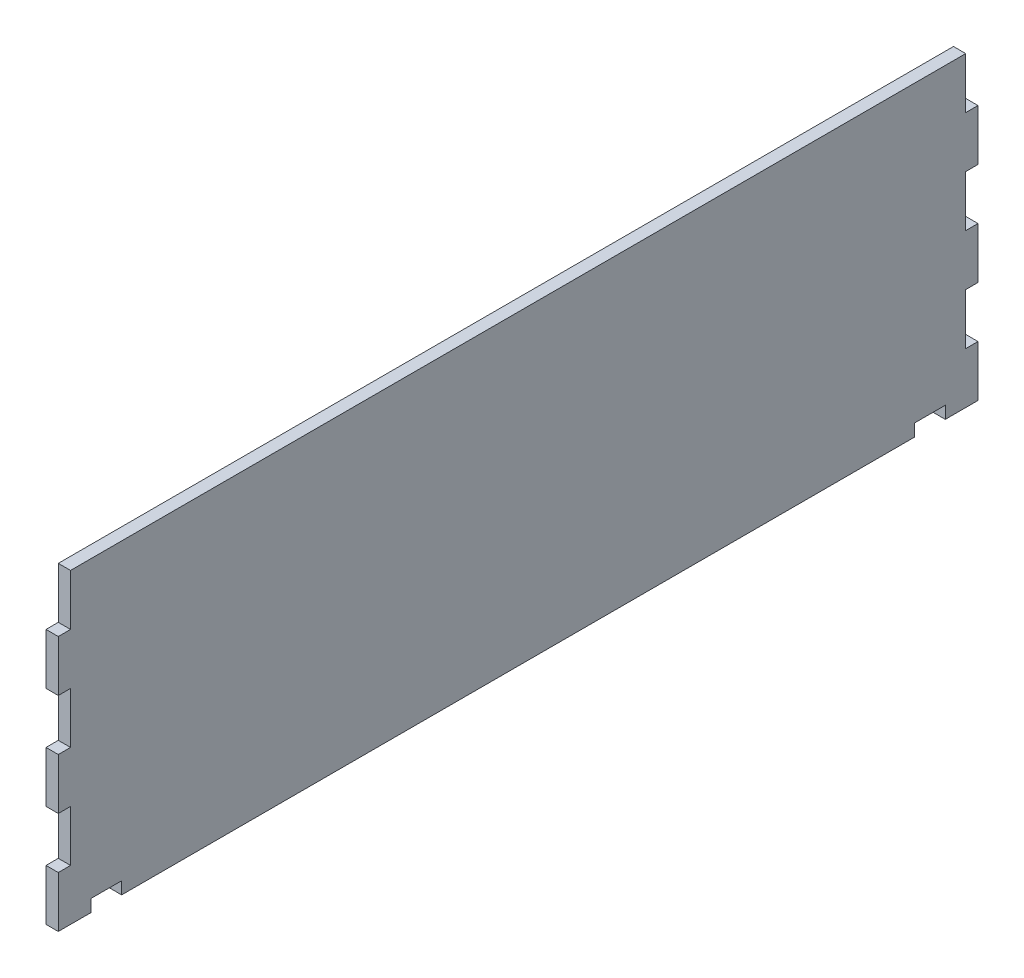
SolidWorks part; units mm, degrees
ref_plane "Front" through (0, 0, 0) normal (0, 0, 1) x (1, 0, 0)
ref_plane "Top" through (0, 0, 0) normal (0, 1, 0) x (1, 0, 0)
ref_plane "Right" through (0, 0, 0) normal (1, 0, 0) x (0, 0, -1)
sketch "Sketch1" plane through (0, 0, 0) normal (1, 0, 0) x (0, 0, -1)
  line L1 (0, 0) -> (-450, 0)
  line L2 (0, 0) -> (0, 150)
  line L3 (0, 150) -> (-450, 150)
  line L4 (-450, 0) -> (-450, 150)
  dimension "D1" = 450
  dimension "D2" = 150
extrude "Boss-Extrude1" add sketch "Sketch1" along normal blind 6
sketch "Sketch2" plane through (6, 0, 0) normal (1, 0, 0) x (0, 0, -1)
  line L0 (-450, 150) -> (-450, 0) construction
  line L1 (-450, 150) -> (-444, 150)
  line L2 (-450, 150) -> (-450, 125)
  line L3 (-450, 125) -> (-444, 125)
  line L4 (-444, 150) -> (-444, 125)
  line L5 (0, 150) -> (-450, 150) construction
  dimension "D1" = 6
  dimension "D2" = 25
extrude "Cut-Extrude1" cut sketch "Sketch2" against normal through all
pattern_linear "LPattern1" count 3 spacing 50 along (0, -1, 0) count 2 spacing 444 along (0, 0, -1) of "Cut-Extrude1"
sketch "Sketch3" plane through (6, 0, 0) normal (1, 0, 0) x (0, 0, -1)
  line L0 (-450, 0) -> (0, 0) construction
  line L1 (-434, 0) -> (-419, 0)
  line L2 (-434, 0) -> (-434, 6)
  line L3 (-434, 6) -> (-419, 6)
  line L4 (-419, 0) -> (-419, 6)
  line L6 (-444, 25) -> (-444, 50) construction
  dimension "D1" = 10
  dimension "D2" = 15
  dimension "D3" = 6
extrude "Cut-Extrude2" cut sketch "Sketch3" against normal through all
pattern_linear "LPattern2" count 2 spacing 403 along (0, 0, -1) of "Cut-Extrude2"
